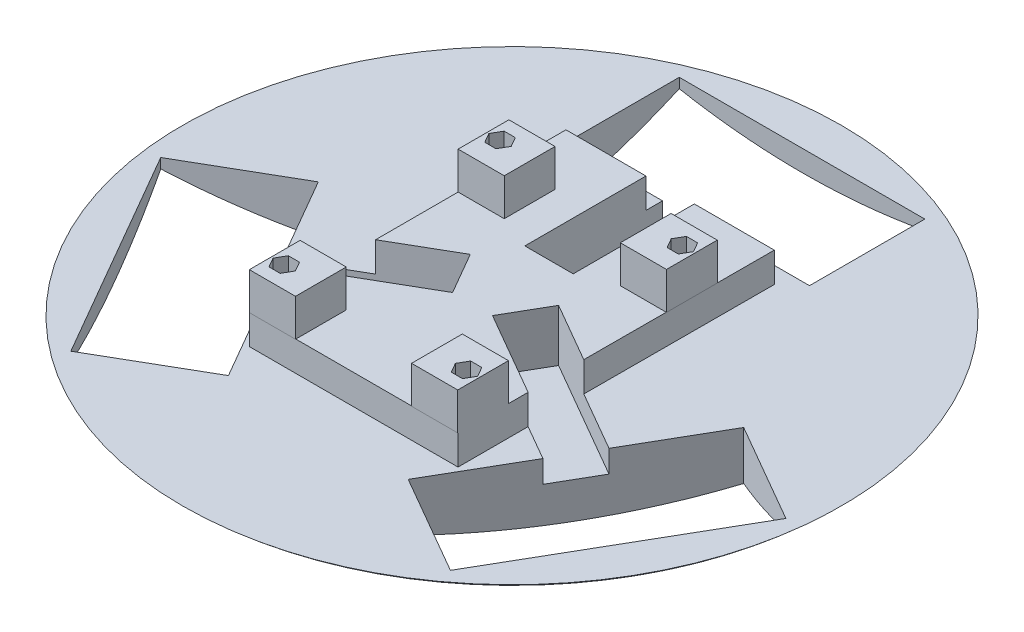
SolidWorks part; units mm, degrees
ref_plane "Front Plane" through (0, 0, 0) normal (0, 0, 1) x (1, 0, 0)
ref_plane "Top Plane" through (0, 0, 0) normal (0, 1, 0) x (1, 0, 0)
ref_plane "Right Plane" through (0, 0, 0) normal (1, 0, 0) x (0, 0, -1)
sketch "Sketch2" plane through (0, 0, 0) normal (0, 1, 0) x (1, 0, 0)
  line L0 (0, -68.0098) -> (0, 65.7503) construction
  line L1 (-33, 77.9495) -> (33, 77.9495)
  line L2 (-33, 77.9495) -> (-33, 46.9495)
  line L3 (-33, 46.9495) -> (33, 46.9495)
  line L4 (33, 77.9495) -> (33, 46.9495)
  line L5 (-33, 77.9495) -> (33, 46.9495) construction
  line L6 (-33, 46.9495) -> (33, 77.9495) construction
  line L7 (-70.2148, 0) -> (95.7201, 0) construction
  line L8 (0, 0) -> (-72.5813, -41.9048) construction
  line L9 (0, 0) -> (72.5813, -41.9048) construction
  line L10 (84.0062, -10.3959) -> (51.0062, -67.5536)
  line L11 (57.1594, 5.1041) -> (24.1594, -52.0536)
  line L12 (84.0062, -10.3959) -> (57.1594, 5.1041)
  line L13 (51.0062, -67.5536) -> (24.1594, -52.0536)
  line L14 (-51.0062, -67.5536) -> (-84.0062, -10.3959)
  line L15 (-24.1594, -52.0536) -> (-57.1594, 5.1041)
  line L16 (-51.0062, -67.5536) -> (-24.1594, -52.0536)
  line L17 (-84.0062, -10.3959) -> (-57.1594, 5.1041)
  line L18 (-6.5, -8.0505) -> (6.5, 46.9495) construction
  line L19 (-6.5, 46.9495) -> (6.5, 46.9495)
  line L20 (-6.5, 46.9495) -> (-6.5, -8.0505)
  line L21 (-6.5, -8.0505) -> (6.5, -8.0505)
  line L22 (6.5, 46.9495) -> (6.5, -8.0505)
  line L23 (-6.5, 46.9495) -> (6.5, -8.0505) construction
  line L24 (31.4023, -15.1408) -> (6.5, -0.7634)
  line L25 (-6.1216, -8.0505) -> (0, 2.5524)
  line L26 (24.9023, -26.3991) -> (0, -12.0218)
  line L27 (-25.0514, -26.4852) -> (0, -12.0218)
  line L28 (0, 2.5524) -> (6.1216, -8.0505)
  line L29 (-33.4324, -16.3129) -> (-6.5, -0.7634)
  circle A2 centre (0, 0) radius 16 construction
  point P3 (0, 19.4495)
  point P4 (0, 46.9495)
  point P6 (0, 62.4495)
  point P13 (0, 0)
  point P33 (0, 0)
  point P41 (0, -4.5162)
  dimension "D1" = 55
  dimension "D2" = 13
  dimension "D3" = 32
  dimension "D5" = 66
  dimension "D6" = 120
  dimension "D7" = 31
  dimension "D8" = 3
  dimension "D4" = 3
sketch "Sketch3" plane through (0, 0, 0) normal (1, 0, 0) x (0, 0, -1)
  line L0 (0, 83.7838) -> (0, -101.0811) construction
  line L1 (-115.9459, 0) -> (127.2973, 0) construction
  line L5 (0, 20) -> (0, 0)
  line L6 (88.569, 20) -> (0, 20)
  arc A3 (84.754, 17.3868) -> (0, 0) centre (7.3808, 179.2865) cw
  arc A4 (84.754, 17.3868) -> (88.569, 20) centre (78.286, 30.9207) ccw
  point P13 (90, 5.0684)
  dimension "D5" = 179.4384
  dimension "D1" = 15
  dimension "D2" = 20
  dimension "D3" = 20
  dimension "D4" = 90
revolve "Revolve1" add sketch "Sketch3" angle 360 about L5
extrude "Cut-Extrude1" cut sketch "Sketch2" along normal blind 40 contours L3 L4 L1 L2 | L15 L17 L14 L16 | L11 L13 L10 L12
sketch "Sketch4" plane through (0, 20, 0) normal (0, 1, 0) x (1, 0, 0)
  line L1 (-6.5, 46.9495) -> (6.5, 46.9495)
  line L2 (-6.5, 46.9495) -> (-6.5, 9.9495)
  line L3 (-6.5, 9.9495) -> (6.5, 9.9495)
  line L4 (6.5, 46.9495) -> (6.5, 9.9495)
  line L5 (-6.5, 46.9495) -> (6.5, 9.9495) construction
  line L6 (-6.5, 9.9495) -> (6.5, 46.9495) construction
  line L7 (43.9094, -17.8456) -> (37.4094, -29.1039)
  line L8 (-57.1594, 5.1041) -> (-24.1594, -52.0536) construction
  line L9 (-33, 46.9495) -> (33, 46.9495) construction
  line L10 (57.1594, 5.1041) -> (24.1594, -52.0536) construction
  line L26 (43.9094, -17.8456) -> (11.8665, 0.6544)
  line L27 (37.4094, -29.1039) -> (5.3665, -10.6039)
  line L28 (11.8665, 0.6544) -> (5.3665, -10.6039)
  line L29 (-37.4094, -29.1039) -> (-43.9094, -17.8456)
  line L30 (-37.4094, -29.1039) -> (-5.3665, -10.6039)
  line L31 (-43.9094, -17.8456) -> (-11.8665, 0.6544)
  line L32 (-5.3665, -10.6039) -> (-11.8665, 0.6544)
  line L33 (51.0062, -67.5536) -> (40.4434, -61.4551)
  line L34 (51.0062, -67.5536) -> (24.1594, -52.0536) construction
  line L35 (51.0062, -67.5536) -> (84.0062, -10.3959)
  line L36 (84.0062, -10.3959) -> (73.4434, -4.2974)
  line L37 (84.0062, -10.3959) -> (57.1594, 5.1041) construction
  circle A0 centre (0, 0) radius 88.569 construction
  circle A1 centre (0, 0) radius 73.569 construction
  arc A2 (40.4434, -61.4551) -> (73.4434, -4.2974) centre (0, 0) ccw
  circle A3 centre (0, 0) radius 84.647
  point P0 (0, 28.4495)
  point P5 (0, 46.9495)
  point P22 (0, 0)
  point P23 (0, 4.0327)
  point P32 (-2.3282, 4.0326)
  line M8 (-57.1594, 5.1041) -> (-24.1594, -52.0536)
  line M13 (24.1594, -52.0536) -> (57.1594, 5.1041)
  line M17 (33, 46.9495) -> (-33, 46.9495)
  dimension "D4" = 177.1379
  dimension "D5" = 147.1379
  dimension "D6" = 169.2941
  dimension "D1" = 13
  dimension "D2" = 37
  dimension "D3" = 15
extrude "Cut-Extrude2" cut sketch "Sketch4" against normal blind 6 contours L4 L2 L3 M17 | L30 L32 L31 M8 | L26 L28 L27 M13 region at (0, 20, -28.4495) region at (24.638, 20, 14.2247) region at (-24.638, 20, 14.2247)
sketch "Sketch5" plane through (0, 20, 0) normal (0, 1, 0) x (1, 0, 0)
  line L1 (-28, 42.5) -> (-6.5, 42.5)
  line L2 (-28, 42.5) -> (-28, -8.6603)
  line L3 (-28, -42.5) -> (28, -42.5)
  line L5 (-28, 42.5) -> (28, -42.5) construction
  line L6 (-28, -42.5) -> (28, 42.5) construction
  line L7 (-37.4094, -29.1039) -> (-5.3665, -10.6039) construction
  line L10 (-43.9094, -17.8456) -> (-11.8665, 0.6544) construction
  line L12 (37.4094, -29.1039) -> (5.3665, -10.6039) construction
  line L18 (6.5, 46.9495) -> (6.5, 9.9495) construction
  line L19 (6.5, 46.9495) -> (6.5, 9.9495) construction
  line L20 (-28, -23.6714) -> (-28, -42.5)
  line L21 (28, -23.6714) -> (28, -42.5)
  line L22 (6.5, 42.5) -> (28, 42.5)
  line L23 (0, 13.9495) -> (0, -42.8187) construction
  line L24 (28, 42.5) -> (27.888, -8.5956)
  line L26 (-6.5, 46.9495) -> (-6.5, 9.9495) construction
  line L27 (43.9094, -17.8456) -> (11.8665, 0.6544) construction
  line L28 (27.888, -8.5956) -> (11.8665, 0.6544)
  line L29 (11.8665, 0.6544) -> (5.3665, -10.6039)
  line L30 (-28, -8.6603) -> (-11.8665, 0.6544)
  line L31 (-11.8665, 0.6544) -> (-5.3665, -10.6039)
  line L32 (-6.5, 42.5) -> (-6.5, 9.9495)
  line L33 (-6.5, 9.9495) -> (6.5, 9.9495)
  line L34 (-5.3665, -10.6039) -> (-28, -23.6714)
  line L35 (5.3665, -10.6039) -> (28, -23.6714)
  line L36 (6.5, 9.9495) -> (6.5, 42.5)
  line L40 (0, -51.0669) -> (0, 44.2573) construction
  line L41 (-47.7731, 0) -> (43.2855, 0) construction
  point P0 (0, 0)
  dimension "D1" = 56
  dimension "D2" = 85
extrude "Boss-Extrude1" add sketch "Sketch5" along normal blind 8
sketch "Sketch6" plane through (0, 28, 0) normal (0, 1, 0) x (1, 0, 0)
  line L0 (-15.5977, 13.519) -> (-15.5977, 27.1605)
  line L1 (-15.5977, 27.1605) -> (-28, 27.1605)
  line L2 (-28, 27.1605) -> (-28, 13.519)
  line L3 (-28, 13.519) -> (-15.5977, 13.519)
  line L4 (-28, 42.5) -> (-28, -8.6603) construction
  line L5 (21.4978, 21.2855) -> (22.9989, 23.8855)
  line L6 (0, -54.2519) -> (0, 64.1127) construction
  line L7 (-46.6508, -7.7145) -> (37.9333, -7.7145) construction
  line L8 (28, 13.519) -> (15.5977, 13.519)
  line L9 (15.5977, 13.519) -> (15.5977, 27.1605)
  line L10 (15.5977, 27.1605) -> (28, 27.1605)
  line L11 (28, 27.1605) -> (28, 13.519)
  line L12 (15.5977, -28.948) -> (15.5977, -42.5894)
  line L13 (28, -28.948) -> (15.5977, -28.948)
  line L14 (28, -42.5894) -> (28, -28.948)
  line L15 (15.5977, -42.5894) -> (28, -42.5894)
  line L16 (-28, -42.5894) -> (-28, -28.948)
  line L17 (-28, -28.948) -> (-15.5977, -28.948)
  line L18 (-15.5977, -28.948) -> (-15.5977, -42.5894)
  line L19 (-15.5977, -42.5894) -> (-28, -42.5894)
  line L20 (-21.4978, 21.2855) -> (-22.9989, 23.8855)
  line L21 (-22.9989, 23.8855) -> (-26.0011, 23.8855)
  line L22 (-26.0011, 23.8855) -> (-27.5022, 21.2855)
  line L23 (-27.5022, 21.2855) -> (-26.0011, 18.6855)
  line L24 (-26.0011, 18.6855) -> (-22.9989, 18.6855)
  line L25 (-22.9989, 18.6855) -> (-21.4978, 21.2855)
  line L26 (22.9989, 18.6855) -> (21.4978, 21.2855)
  line L27 (26.0011, 18.6855) -> (22.9989, 18.6855)
  line L28 (27.5022, 21.2855) -> (26.0011, 18.6855)
  line L29 (26.0011, 23.8855) -> (27.5022, 21.2855)
  line L30 (22.9989, 23.8855) -> (26.0011, 23.8855)
  line L31 (-21.4978, -36.7145) -> (-22.9989, -39.3145)
  line L32 (-22.9989, -39.3145) -> (-26.0011, -39.3145)
  line L33 (-26.0011, -39.3145) -> (-27.5022, -36.7145)
  line L34 (-27.5022, -36.7145) -> (-26.0011, -34.1145)
  line L35 (-26.0011, -34.1145) -> (-22.9989, -34.1145)
  line L36 (-22.9989, -34.1145) -> (-21.4978, -36.7145)
  line L37 (26.0011, -39.3145) -> (27.5022, -36.7145)
  line L38 (22.9989, -39.3145) -> (26.0011, -39.3145)
  line L39 (21.4978, -36.7145) -> (22.9989, -39.3145)
  line L40 (22.9989, -34.1145) -> (21.4978, -36.7145)
  line L41 (26.0011, -34.1145) -> (22.9989, -34.1145)
  line L42 (27.5022, -36.7145) -> (26.0011, -34.1145)
  circle A0 centre (-24.5, 21.2855) radius 2.6 construction
  dimension "D3" = 5.2
  dimension "D1" = 29
  dimension "D2" = 24.5
  dimension "D4" = 15.5977
  dimension "D5" = 13.6415
extrude "Boss-Extrude2" add sketch "Sketch6" along normal blind 10
sketch "Sketch7" plane through (-3.25, 0, -5.6292) normal (0.5, 0, 0.866) x (0.866, 0, -0.5)
  line L0 (-46.9495, 14) -> (-46.9495, 33.5813) construction
  line L1 (-24.7351, 23.7906) -> (-46.9495, 23.7906)
  line L3 (-46.9495, 23.7906) -> (-46.9495, 27.9906)
  line L4 (-46.9495, 27.9906) -> (-24.7351, 27.9906)
  line L5 (-24.7351, 27.9906) -> (-24.7351, 23.7906)
  dimension "D1" = 4.2
  dimension "D2" = 0
  dimension "D3" = 22.2144
